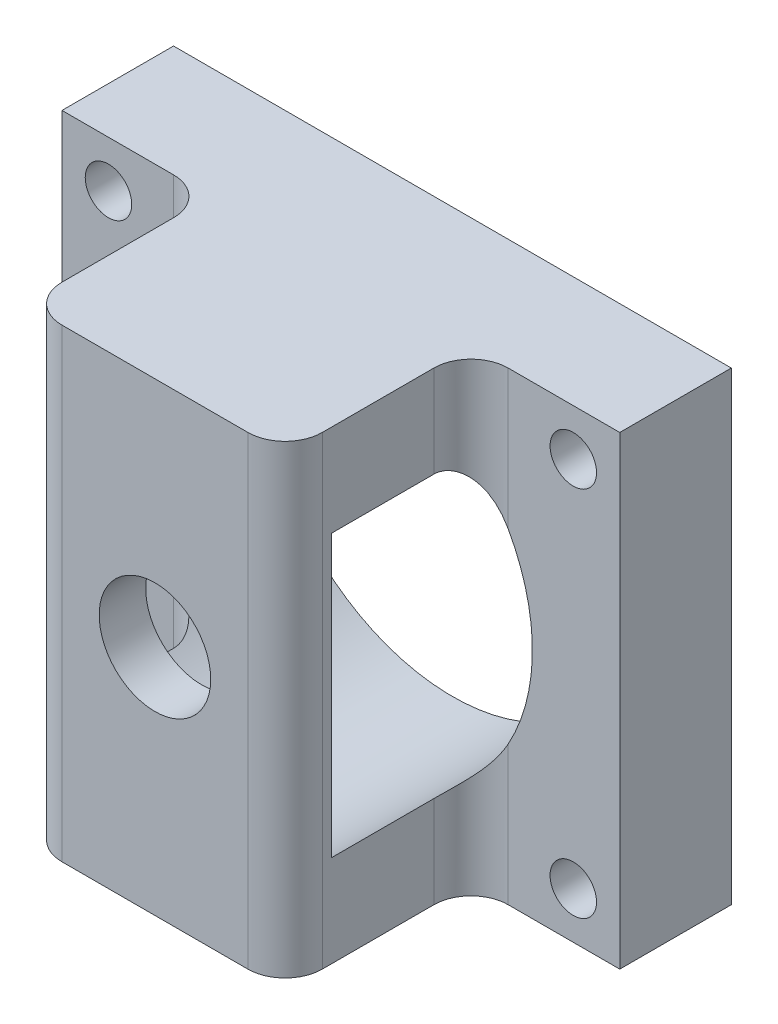
SolidWorks part; units mm, degrees
ref_plane "Front Plane" through (0, 0, 0) normal (0, 0, 1) x (1, 0, 0)
ref_plane "Top Plane" through (0, 0, 0) normal (0, 1, 0) x (1, 0, 0)
ref_plane "Right Plane" through (0, 0, 0) normal (1, 0, 0) x (0, 0, -1)
sketch "Sketch1" plane through (0, 0, 0) normal (0, 0, 1) x (1, 0, 0)
  line L0 (-12.5, 10) -> (12.5, -10) construction
  line L1 (-15, -12.5) -> (15, -12.5)
  line L2 (-15, -12.5) -> (-15, 12.5)
  line L3 (-15, 12.5) -> (15, 12.5)
  line L4 (15, -12.5) -> (15, 12.5)
  line L5 (-15, -12.5) -> (15, 12.5) construction
  line L6 (-15, 12.5) -> (15, -12.5) construction
  circle A0 centre (-12.5, 10) radius 1.25
  circle A1 centre (12.5, 10) radius 1.25
  circle A2 centre (-12.5, -10) radius 1.25
  circle A3 centre (12.5, -10) radius 1.25
  circle A4 centre (0, 0) radius 3
  point P0 (0, 0)
  point P14 (0, 0)
  dimension "D3" = 2.5
  dimension "D6" = 6
  dimension "D1" = 25
  dimension "D2" = 30
  dimension "D4" = 25
  dimension "D5" = 20
extrude "Main" add sketch "Sketch1" along normal blind 16
sketch "Sketch2" plane through (0, 0, 0) normal (0, 0, 1) x (1, 0, 0)
  circle A0 centre (0, 0) radius 10.3
  dimension "D1" = 20.6
extrude "CentralHole" cut sketch "Sketch2" along normal blind 13.5
sketch "Sketch5" plane through (0, 0, 16) normal (0, 0, 1) x (1, 0, 0)
  line L0 (15, 12.5) -> (-15, 12.5) construction
  line L1 (15, -12.5) -> (7, -12.5)
  line L2 (15, -12.5) -> (15, 12.5)
  line L3 (15, 12.5) -> (7, 12.5)
  line L4 (7, -12.5) -> (7, 12.5)
  line L6 (-15, -12.5) -> (-7, -12.5)
  line L7 (-15, -12.5) -> (-15, 12.5)
  line L8 (-15, 12.5) -> (-7, 12.5)
  line L9 (-7, -12.5) -> (-7, 12.5)
  dimension "D1" = 8
  dimension "D2" = 8
extrude "Cut-Extrude3" cut sketch "Sketch5" against normal blind 10
fillet "Fillet1" radius 2 6 edges at (-7, 0, 16) (7, 0, 16) (-7, -10.0279, 6) (-7, 10.0279, 6) (7, 10.0279, 6) (7, -10.0279, 6)
